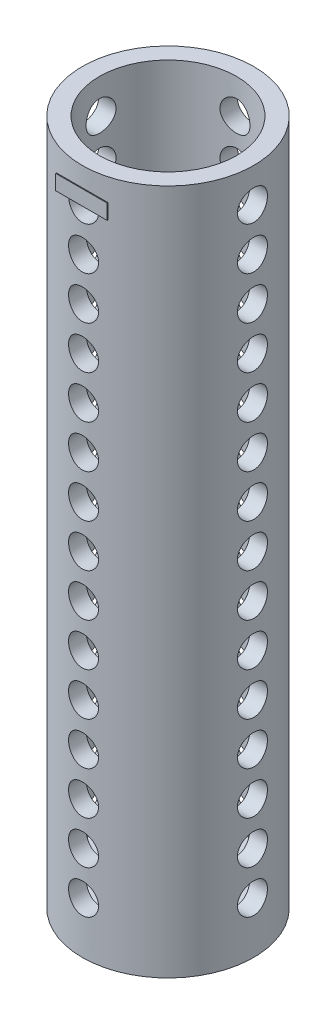
SolidWorks part; units mm, degrees
ref_plane "Front Plane" through (0, 0, 0) normal (0, 0, 1) x (1, 0, 0)
ref_plane "Top Plane" through (0, 0, 0) normal (0, 1, 0) x (1, 0, 0)
ref_plane "Right Plane" through (0, 0, 0) normal (1, 0, 0) x (0, 0, -1)
sketch "Sketch1" plane through (0, 0, 0) normal (0, 1, 0) x (1, 0, 0)
  circle A0 centre (0, 0) radius 10
  circle A1 centre (0, 0) radius 8
  dimension "D1" = 20
  dimension "D2" = 2
extrude "Boss-Extrude1" add sketch "Sketch1" along normal blind 80
sketch "Sketch2" plane through (0, 0, 0) normal (0, 0, 1) x (1, 0, 0)
  line L0 (0, 80) -> (0, 0) construction
  line L1 (10, 80) -> (-10, 80) construction
  line L2 (8, 80) -> (-8, 80) construction
  circle A0 centre (0, 76) radius 1.75
  circle A1 centre (0, 71) radius 1.75
  circle A2 centre (0, 66) radius 1.75
  circle A3 centre (0, 61) radius 1.75
  circle A4 centre (0, 56) radius 1.75
  circle A5 centre (0, 51) radius 1.75
  circle A6 centre (0, 46) radius 1.75
  circle A7 centre (0, 41) radius 1.75
  circle A8 centre (0, 36) radius 1.75
  circle A9 centre (0, 31) radius 1.75
  circle A10 centre (0, 26) radius 1.75
  circle A11 centre (0, 21) radius 1.75
  circle A12 centre (0, 16) radius 1.75
  circle A13 centre (0, 11) radius 1.75
  circle A14 centre (0, 6) radius 1.75
  dimension "D1" = 4
  dimension "D2" = 3.5
  dimension "D3" = 9
  dimension "D4" = 7
extrude "Cut-Extrude1" cut sketch "Sketch2" against normal blind 10 and the other way blind 10
pattern_circular "CirPattern1" count 4 over 360 about axis through (0, 80, 0) along (0, 1, 0) of "Cut-Extrude1"
sketch "Sketch3" plane through (0, 0, 0) normal (0, -1, 0) x (1, 0, 0)
  circle A0 centre (0, 0) radius 8
extrude "Boss-Extrude2" add sketch "Sketch3" against normal blind 4
sketch "Sketch4" plane through (0, 0, 0) normal (0, -1, 0) x (1, 0, 0)
  circle A0 centre (0, 0) radius 1.75
  dimension "D1" = 3.5
extrude "Cut-Extrude2" cut sketch "Sketch4" against normal blind 5
ref_plane "Plane1" through (0, 0, 10) normal (0, 0, 1) x (1, 0, 0)
sketch "Sketch6" plane through (0, 0, 10) normal (0, 0, 1) x (1, 0, 0)
  line L0 (0, 77.75) -> (0, 76) construction
  line L1 (-3, 77.75) -> (-3, 76)
  line L2 (3, 77.75) -> (3, 76)
  line L3 (-3, 76) -> (3, 76)
  line L4 (-3, 77.75) -> (3, 77.75)
  circle A0 centre (0, 76) radius 1.75 construction
  dimension "D1" = 3
  dimension "D2" = 3
extrude "Boss-Extrude3" add sketch "Sketch6" along normal blind 0.1 separate body
